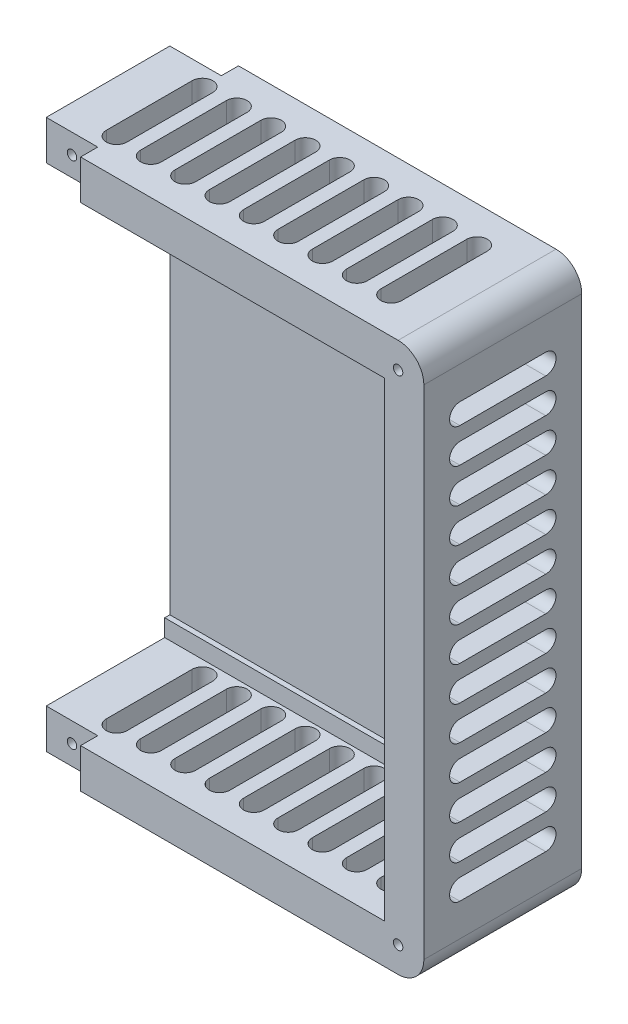
SolidWorks part; units mm, degrees
ref_plane "Front Plane" through (0, 0, 0) normal (0, 0, 1) x (1, 0, 0)
ref_plane "Top Plane" through (0, 0, 0) normal (0, 1, 0) x (1, 0, 0)
ref_plane "Right Plane" through (0, 0, 0) normal (1, 0, 0) x (0, 0, -1)
sketch "Sketch1" plane through (0, 0, 0) normal (0, 0, 1) x (1, 0, 0)
  line L1 (-115, 80) -> (115, 80)
  line L2 (-115, 80) -> (-115, -80)
  line L3 (-115, -80) -> (115, -80)
  line L4 (115, 80) -> (115, -80)
  line L5 (-115, 80) -> (115, -80) construction
  line L6 (-115, -80) -> (115, 80) construction
  point P0 (0, 0)
  dimension "D1" = 230
  dimension "D2" = 160
extrude "Boss-Extrude1" add sketch "Sketch1" along normal blind 46
shell "Shell1" thickness 11.5 removed face at (0, 0, 46)
sketch "Sketch2" plane through (-115, 0, 0) normal (-1, 0, 0) x (0, 0, 1)
  line L1 (34.5, -23.5) -> (18.5, -23.5)
  line L2 (34.5, -23.5) -> (34.5, -58.5)
  line L3 (34.5, -58.5) -> (18.5, -58.5)
  line L4 (18.5, -23.5) -> (18.5, -58.5)
  line L5 (34.5, -23.5) -> (18.5, -58.5) construction
  line L6 (34.5, -58.5) -> (18.5, -23.5) construction
  line L7 (46, -80) -> (0, -80) construction
  line L9 (46, 80) -> (0, 80) construction
  line L10 (46, 80) -> (46, -80) construction
  circle A0 centre (28.5, -15) radius 3.25
  circle A1 centre (28, 20) radius 9
  point P0 (26.5, -41)
  dimension "D4" = 8.5
  dimension "D6" = 6.5
  dimension "D7" = 18
  dimension "D1" = 56.5
  dimension "D2" = 35
  dimension "D3" = 17.5
  dimension "D5" = 16
  dimension "D8" = 60
  dimension "D9" = 18
  dimension "D10" = 11.5
extrude "Cut-Extrude1" cut sketch "Sketch2" against normal up to surface (11.5 mm away) up to face at (-103.5, 0, 28.75)
sketch "Sketch3" plane through (0, 0, 46) normal (0, 0, 1) x (1, 0, 0)
  line L1 (-115, -80) -> (115, -80) construction
  line L2 (0, 80) -> (-115, 80)
  line L3 (0, 80) -> (0, -80)
  line L4 (0, -80) -> (-115, -80)
  line L5 (-115, 80) -> (-115, -80)
  line L7 (-115, 80) -> (-115, -80) construction
  dimension "D1" = 115
extrude "Cut-Extrude3" cut sketch "Sketch3" against normal up to surface (46 mm away) up to face at (0, 0, 0)
ref_plane "Plane1" through (0, 0, 23) normal (0, 0, 1) x (1, 0, 0)
sketch "Sketch12" plane through (0, 0, 11.5) normal (0, 0, 1) x (1, 0, 0)
  line L0 (103.5, 68.5) -> (0, 68.5) construction
  line L1 (103.5, 68.5) -> (0, 68.5)
  line L2 (103.5, 68.5) -> (103.5, -68.5)
  line L3 (103.5, -68.5) -> (0, -68.5)
  line L4 (0, 68.5) -> (0, -68.5)
  line L5 (103.5, 68.5) -> (0, -68.5) construction
  line L6 (103.5, -68.5) -> (0, 68.5) construction
  line L7 (103.5, -68.5) -> (103.5, 68.5) construction
  line L8 (0, -68.5) -> (103.5, -68.5) construction
  line L9 (0, -68.5) -> (0, 68.5) construction
  point P0 (51.75, 0)
extrude "Cut-Extrude11" cut sketch "Sketch12" against normal blind 5
sketch "Sketch13" plane through (0, 0, 6.5) normal (0, 0, 1) x (1, 0, 0)
  line L0 (103.5, -68.5) -> (103.5, 68.5) construction
  line L1 (91, 63.5) -> (0, 63.5)
  line L2 (98.5, 56) -> (98.5, -56)
  line L3 (91, -63.5) -> (0, -63.5)
  line L4 (0, 63.5) -> (0, -63.5)
  line L5 (98.5, 63.5) -> (0, -63.5) construction
  line L6 (98.5, -63.5) -> (0, 63.5) construction
  line L7 (103.5, 68.5) -> (0, 68.5) construction
  line L9 (0, -68.5) -> (103.5, -68.5) construction
  arc A0 (98.5, -56) -> (91, -63.5) centre (91, -56) cw
  arc A1 (91, 63.5) -> (98.5, 56) centre (91, 56) cw
  point P0 (49.25, 0)
  dimension "D3" = 7.5
  dimension "D1" = 5
  dimension "D2" = 5
  dimension "D4" = 5
extrude "Cut-Extrude12" cut sketch "Sketch13" against normal blind 1.5
sketch "Sketch14" plane through (0, 80, 0) normal (0, 1, 0) x (1, 0, 0)
  line L0 (98, -35.5) -> (98, -10.5)
  line L1 (92, -35.5) -> (92, -10.5)
  line L3 (115, -46) -> (115, 0) construction
  line L4 (115, -46) -> (0, -46) construction
  line L6 (88, -35.5) -> (88, -10.5)
  line L7 (82, -35.5) -> (82, -10.5)
  line L8 (78, -35.5) -> (78, -10.5)
  line L9 (72, -35.5) -> (72, -10.5)
  line L10 (68, -35.5) -> (68, -10.5)
  line L11 (62, -35.5) -> (62, -10.5)
  line L12 (58, -35.5) -> (58, -10.5)
  line L13 (52, -35.5) -> (52, -10.5)
  line L14 (48, -35.5) -> (48, -10.5)
  line L15 (42, -35.5) -> (42, -10.5)
  line L16 (38, -35.5) -> (38, -10.5)
  line L17 (32, -35.5) -> (32, -10.5)
  line L18 (28, -35.5) -> (28, -10.5)
  line L19 (22, -35.5) -> (22, -10.5)
  line L20 (18, -35.5) -> (18, -10.5)
  line L21 (12, -35.5) -> (12, -10.5)
  arc A0 (98, -35.5) -> (92, -35.5) centre (95, -35.5) cw
  arc A1 (92, -10.5) -> (98, -10.5) centre (95, -10.5) cw
  arc A2 (88, -35.5) -> (82, -35.5) centre (85, -35.5) cw
  arc A3 (82, -10.5) -> (88, -10.5) centre (85, -10.5) cw
  arc A4 (78, -35.5) -> (72, -35.5) centre (75, -35.5) cw
  arc A5 (72, -10.5) -> (78, -10.5) centre (75, -10.5) cw
  arc A6 (68, -35.5) -> (62, -35.5) centre (65, -35.5) cw
  arc A7 (62, -10.5) -> (68, -10.5) centre (65, -10.5) cw
  arc A8 (58, -35.5) -> (52, -35.5) centre (55, -35.5) cw
  arc A9 (52, -10.5) -> (58, -10.5) centre (55, -10.5) cw
  arc A10 (48, -35.5) -> (42, -35.5) centre (45, -35.5) cw
  arc A11 (42, -10.5) -> (48, -10.5) centre (45, -10.5) cw
  arc A12 (38, -35.5) -> (32, -35.5) centre (35, -35.5) cw
  arc A13 (32, -10.5) -> (38, -10.5) centre (35, -10.5) cw
  arc A14 (28, -35.5) -> (22, -35.5) centre (25, -35.5) cw
  arc A15 (22, -10.5) -> (28, -10.5) centre (25, -10.5) cw
  arc A16 (18, -35.5) -> (12, -35.5) centre (15, -35.5) cw
  arc A17 (12, -10.5) -> (18, -10.5) centre (15, -10.5) cw
  point P8 (95, -38.5)
  dimension "D2" = 3
  dimension "D3" = 17
  dimension "D1" = 25
  dimension "D4" = 7.5
  dimension "D5" = 9
extrude "Cut-Extrude13" cut sketch "Sketch14" against normal blind 12
mirror "Mirror9" about plane through (0, 0, 0) normal (0, 1, 0) of "Cut-Extrude13"
sketch "Sketch15" plane through (115, 0, 0) normal (1, 0, 0) x (0, 0, -1)
  line L0 (-35.5, -63) -> (-10.5, -63)
  line L1 (-10.5, -57) -> (-35.5, -57)
  line L2 (-46, -80) -> (0, -80) construction
  line L3 (-46, -80) -> (-46, 80) construction
  line L9 (-35.5, -53) -> (-10.5, -53)
  line L10 (-10.5, -47) -> (-35.5, -47)
  line L11 (-35.5, -43) -> (-10.5, -43)
  line L12 (-10.5, -37) -> (-35.5, -37)
  line L13 (-35.5, -33) -> (-10.5, -33)
  line L14 (-10.5, -27) -> (-35.5, -27)
  line L15 (-35.5, -23) -> (-10.5, -23)
  line L16 (-10.5, -17) -> (-35.5, -17)
  line L17 (-35.5, -13) -> (-10.5, -13)
  line L18 (-10.5, -7) -> (-35.5, -7)
  line L19 (-35.5, -3) -> (-10.5, -3)
  line L20 (-10.5, 3) -> (-35.5, 3)
  line L21 (-35.5, 7) -> (-10.5, 7)
  line L22 (-10.5, 13) -> (-35.5, 13)
  line L23 (-35.5, 17) -> (-10.5, 17)
  line L24 (-10.5, 23) -> (-35.5, 23)
  line L25 (-35.5, 27) -> (-10.5, 27)
  line L26 (-10.5, 33) -> (-35.5, 33)
  line L27 (-35.5, 37) -> (-10.5, 37)
  line L28 (-10.5, 43) -> (-35.5, 43)
  line L29 (-35.5, 47) -> (-10.5, 47)
  line L30 (-10.5, 53) -> (-35.5, 53)
  line L31 (-35.5, 57) -> (-10.5, 57)
  line L32 (-10.5, 63) -> (-35.5, 63)
  arc A0 (-10.5, -63) -> (-10.5, -57) centre (-10.5, -60) ccw
  arc A1 (-35.5, -57) -> (-35.5, -63) centre (-35.5, -60) ccw
  arc A2 (-35.5, -47) -> (-35.5, -53) centre (-35.5, -50) ccw
  arc A3 (-10.5, -53) -> (-10.5, -47) centre (-10.5, -50) ccw
  arc A4 (-35.5, -37) -> (-35.5, -43) centre (-35.5, -40) ccw
  arc A5 (-10.5, -43) -> (-10.5, -37) centre (-10.5, -40) ccw
  arc A6 (-35.5, -27) -> (-35.5, -33) centre (-35.5, -30) ccw
  arc A7 (-10.5, -33) -> (-10.5, -27) centre (-10.5, -30) ccw
  arc A8 (-35.5, -17) -> (-35.5, -23) centre (-35.5, -20) ccw
  arc A9 (-10.5, -23) -> (-10.5, -17) centre (-10.5, -20) ccw
  arc A10 (-35.5, -7) -> (-35.5, -13) centre (-35.5, -10) ccw
  arc A11 (-10.5, -13) -> (-10.5, -7) centre (-10.5, -10) ccw
  arc A12 (-35.5, 3) -> (-35.5, -3) centre (-35.5, 0) ccw
  arc A13 (-10.5, -3) -> (-10.5, 3) centre (-10.5, 0) ccw
  arc A14 (-35.5, 13) -> (-35.5, 7) centre (-35.5, 10) ccw
  arc A15 (-10.5, 7) -> (-10.5, 13) centre (-10.5, 10) ccw
  arc A16 (-35.5, 23) -> (-35.5, 17) centre (-35.5, 20) ccw
  arc A17 (-10.5, 17) -> (-10.5, 23) centre (-10.5, 20) ccw
  arc A18 (-35.5, 33) -> (-35.5, 27) centre (-35.5, 30) ccw
  arc A19 (-10.5, 27) -> (-10.5, 33) centre (-10.5, 30) ccw
  arc A20 (-35.5, 43) -> (-35.5, 37) centre (-35.5, 40) ccw
  arc A21 (-10.5, 37) -> (-10.5, 43) centre (-10.5, 40) ccw
  arc A22 (-35.5, 53) -> (-35.5, 47) centre (-35.5, 50) ccw
  arc A23 (-10.5, 47) -> (-10.5, 53) centre (-10.5, 50) ccw
  arc A24 (-35.5, 63) -> (-35.5, 57) centre (-35.5, 60) ccw
  arc A25 (-10.5, 57) -> (-10.5, 63) centre (-10.5, 60) ccw
  point P8 (-38.5, -60)
  dimension "D4" = 3
  dimension "D1" = 17
  dimension "D2" = 25
  dimension "D3" = 7.5
  dimension "D5" = 13
extrude "Cut-Extrude14" cut sketch "Sketch15" against normal blind 12
fillet "Fillet1" radius 7.5 2 edges at (115, -80, 23) (115, 80, 23)
sketch "Sketch16" plane through (0, 0, 46) normal (0, 0, 1) x (1, 0, 0)
  line L0 (107.5, 80) -> (0, 80) construction
  line L1 (115, -72.5) -> (115, 72.5) construction
  line L2 (0, -80) -> (107.5, -80) construction
  circle A0 centre (107.5, -72.5) radius 1.375
  circle A1 centre (107.5, 72.5) radius 1.375
  dimension "D1" = 2.75
  dimension "D4" = 2.75
  dimension "D2" = 7.5
  dimension "D3" = 7.5
  dimension "D5" = 7.5
  dimension "D6" = 7.5
extrude "Cut-Extrude15" cut sketch "Sketch16" against normal blind 10
sketch "Sketch17" plane through (0, 0, 46) normal (0, 0, 1) x (1, 0, 0)
  line L0 (0, 68.5) -> (0, 80) construction
  line L1 (15, 68.5) -> (-15, 68.5)
  line L2 (15, 68.5) -> (15, 80)
  line L3 (15, 80) -> (-15, 80)
  line L4 (-15, 68.5) -> (-15, 80)
  line L5 (15, 68.5) -> (-15, 80) construction
  line L6 (15, 80) -> (-15, 68.5) construction
  line L7 (103.5, 68.5) -> (0, 68.5) construction
  line L8 (107.5, 80) -> (0, 80) construction
  point P0 (0, 74.25)
  dimension "D1" = 30
extrude "Cut-Extrude16" cut sketch "Sketch17" against normal blind 5
sketch "Sketch18" plane through (0, 0, 41) normal (0, 0, 1) x (1, 0, 0)
  line L0 (0, 68.5) -> (15, 68.5) construction
  line L1 (0, 80) -> (0, 68.5) construction
  circle A0 centre (7.5, 74.25) radius 1.375
  point P6 (0, 74.25)
  dimension "D1" = 2.75
  dimension "D2" = 5.75
  dimension "D3" = 7.5
extrude "Cut-Extrude17" cut sketch "Sketch18" against normal blind 8
mirror "Mirror10" about plane through (0, 0, 0) normal (0, 1, 0) of "Cut-Extrude16", "Cut-Extrude17"
sketch "Sketch19" plane through (0, 0, 0) normal (0, 0, -1) x (-1, 0, 0)
  line L0 (0, 80) -> (0, -80) construction
  line L1 (-15, -68.5) -> (15, -68.5)
  line L2 (-15, -68.5) -> (-15, -80)
  line L3 (-15, -80) -> (15, -80)
  line L4 (15, -68.5) -> (15, -80)
  line L5 (-15, -68.5) -> (15, -80) construction
  line L6 (-15, -80) -> (15, -68.5) construction
  line L7 (0, -80) -> (-107.5, -80) construction
  point P0 (0, -74.25)
  dimension "D1" = 11.5
  dimension "D2" = 30
extrude "Cut-Extrude18" cut sketch "Sketch19" against normal blind 5
sketch "Sketch20" plane through (0, 0, 5) normal (0, 0, -1) x (-1, 0, 0)
  line L0 (0, -80) -> (0, -68.5) construction
  line L1 (-15, -80) -> (0, -80) construction
  circle A0 centre (-7.5, -74.25) radius 1.375
  dimension "D1" = 2.75
  dimension "D2" = 7.5
  dimension "D3" = 5.75
extrude "Cut-Extrude19" cut sketch "Sketch20" against normal blind 8
mirror "Mirror11" about plane through (0, 0, 0) normal (0, 1, 0) of "Cut-Extrude19", "Cut-Extrude18"
